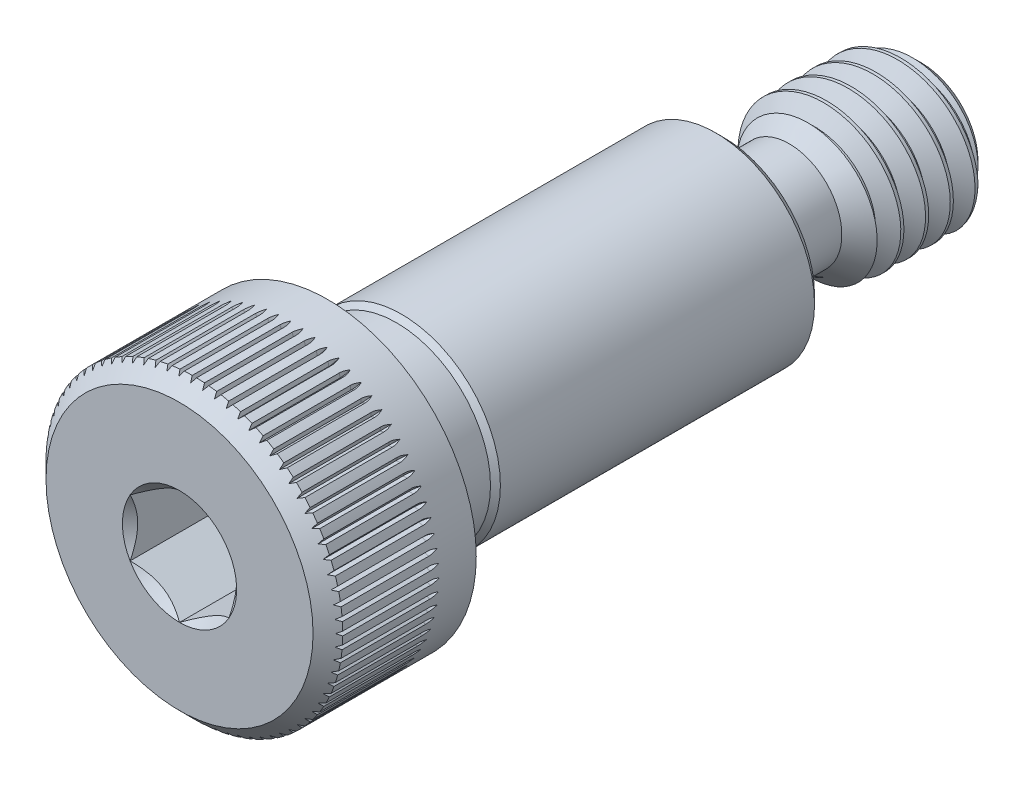
SolidWorks part; units mm, degrees
ref_plane "Front Plane" through (0, 0, 0) normal (0, 0, 1) x (1, 0, 0)
ref_plane "Top Plane" through (0, 0, 0) normal (0, 1, 0) x (1, 0, 0)
ref_plane "Right Plane" through (0, 0, 0) normal (1, 0, 0) x (0, 0, -1)
sketch "Sketch2" plane through (0, 0, 0) normal (1, 0, 0) x (0, 0, -1)
  line L0 (-11.9062, 0) -> (11.9062, 0) construction
  line L1 (-11.9062, 0) -> (-11.9062, 4.7625)
  line L2 (-11.9062, 4.7625) -> (-7.1437, 4.7625)
  line L3 (-7.1437, 4.7625) -> (-7.1437, 3.175)
  line L4 (-7.1437, 3.175) -> (5.5562, 3.175)
  line L5 (5.5562, 2.413) -> (11.9062, 2.413)
  line L6 (11.9062, 2.413) -> (11.9062, 0)
  line L7 (11.8566, 2.4989) -> (12.2535, 1.8115) construction
  line L8 (12.2535, 1.8115) -> (12.6504, 2.4989) construction
  line L9 (12.6504, 2.4989) -> (11.8566, 2.4989) construction
  line L10 (11.9062, 2.413) -> (12.6008, 2.413) construction
  line L11 (12.2535, 2.4989) -> (12.2535, 2.413) construction
  line L12 (12.2535, 2.413) -> (12.2535, 1.8974) construction
  line L13 (12.2535, 1.8974) -> (12.2535, 1.8115) construction
  line L14 (12.2039, 1.8974) -> (12.3031, 1.8974)
  line L15 (11.8814, 2.456) -> (12.6256, 2.456)
  line L16 (12.3031, 1.8974) -> (12.6256, 2.456)
  line L17 (12.2039, 1.8974) -> (11.8814, 2.456)
  line L18 (11.9062, 0) -> (11.9062, -2.413) construction
  line L19 (5.5562, -3.175) -> (5.5562, 0) construction
  line L20 (5.5562, 0) -> (5.5562, 3.175) construction
  line L21 (-11.9062, 0) -> (-11.9062, -4.7625) construction
  point P11 (-4.7815, 3.175)
  point P12 (9.9219, -2.413)
  point P22 (12.2535, 2.456)
  point P23 (4.2862, 0)
  point P25 (-4.2862, 0)
  point P26 (-7.1437, -4.7625)
  point P29 (5.5562, -3.175)
  dimension "Head Height" = 4.7625
  dimension "Shoulder Diameter" = 6.35
  dimension "Screw Size Decimal Equivalent" = 4.826
  dimension "Thread Length" = 6.35
  dimension "Head Diameter" = 9.525
  dimension "Undercut Length" = 2.3622
  dimension "Pitch" = 0.7937
  dimension "D2" = 0.0992
  dimension "D1" = 1.9844
  dimension "D3" = 7.62
  dimension "D4" = 7.62
  dimension "Shoulder Length" = 12.7
sketch "Sketch3" plane through (0, 0, 0) normal (0, 0, 1) x (1, 0, 0)
  line L1 (0, 1.8331) -> (-1.5875, 0.9165)
  line L2 (-1.5875, 0.9165) -> (-1.5875, -0.9165)
  line L3 (-1.5875, -0.9165) -> (0, -1.8331)
  line L4 (0, -1.8331) -> (1.5875, -0.9165)
  line L5 (1.5875, -0.9165) -> (1.5875, 0.9165)
  line L6 (1.5875, 0.9165) -> (0, 1.8331)
  circle A0 centre (0, 0) radius 1.5875 construction
  dimension "Drive Size" = 3.175
sketch "Sketch4" plane through (0, 0, 0) normal (1, 0, 0) x (0, 0, -1)
  line L0 (-7.1437, 4.7625) -> (-11.43, 4.7625)
  line L1 (-11.43, 4.7625) -> (-11.9062, 4.2862)
  line L2 (-7.1437, 4.7625) -> (-7.1437, 3.175)
  line L3 (-7.1437, 3.175) -> (-6.985, 3.0162)
  line L4 (-6.985, 3.0162) -> (-4.9403, 3.0162)
  line L5 (-4.9403, 3.0162) -> (-4.7815, 3.175)
  line L6 (-7.1437, 3.175) -> (5.5562, 3.175) construction
  line L7 (-11.9062, 0) -> (11.9062, 0) construction
  line L8 (-4.7815, 3.175) -> (5.3022, 3.175)
  line L9 (5.3022, 3.175) -> (5.5562, 2.921)
  line L10 (5.5562, 2.921) -> (5.5562, 0)
  line L11 (5.5562, 3.175) -> (5.5562, 2.921) construction
  line L12 (5.5562, 2.921) -> (5.5562, 2.667) construction
  line L13 (5.5562, 2.667) -> (5.5562, 2.413) construction
  line L14 (-11.9062, 4.2862) -> (-11.9062, 0)
  line L15 (-11.9062, 4.7625) -> (-7.1437, 4.7625) construction
  line L16 (-11.9062, 0) -> (5.5562, 0)
  dimension "D1" = 45
  dimension "D2" = 6.0325
  dimension "D3" = 45
  dimension "D4" = 45
  dimension "D5" = 8.5725
revolve "Revolve1" add sketch "Sketch4" angle 360 about L16
sketch "Sketch5" plane through (0, 0, 11.9062) normal (0, 0, 1) x (1, 0, 0)
  line L0 (1.5875, 0.9165) -> (0, 1.8331) construction
  line L1 (1.5875, -0.9165) -> (1.5875, 0.9165) construction
  line L2 (0, -1.8331) -> (1.5875, -0.9165) construction
  line L3 (-1.5875, -0.9165) -> (0, -1.8331) construction
  line L4 (-1.5875, 0.9165) -> (-1.5875, -0.9165) construction
  line L5 (0, 1.8331) -> (-1.5875, 0.9165) construction
  line L6 (1.5875, 0.9165) -> (0, 1.8331)
  line L7 (1.5875, -0.9165) -> (1.5875, 0.9165)
  line L8 (0, -1.8331) -> (1.5875, -0.9165)
  line L9 (-1.5875, -0.9165) -> (0, -1.8331)
  line L10 (-1.5875, 0.9165) -> (-1.5875, -0.9165)
  line L11 (0, 1.8331) -> (-1.5875, 0.9165)
extrude "Cut-Extrude1" cut sketch "Sketch5" against normal blind 3.5719
sketch "Sketch6" plane through (0, 0, 11.9062) normal (0, 0, 1) x (1, 0, 0)
  circle A0 centre (0, 0) radius 1.8331
extrude "Cut-Extrude4" cut sketch "Sketch6" against normal blind 3.5719 draft 45
sketch "Sketch7" plane through (0, 0, 0) normal (1, 0, 0) x (0, 0, -1)
  line L0 (5.5562, 2.413) -> (11.3109, 2.413)
  line L1 (5.5562, 2.413) -> (11.9062, 2.413) construction
  line L2 (11.3109, 2.413) -> (11.9062, 1.8177)
  line L3 (11.9062, 2.413) -> (11.9062, 0) construction
  line L4 (11.9062, 1.8177) -> (11.9062, 0)
  line L5 (11.9062, 0) -> (5.5562, 0)
  line L6 (5.5562, -2.921) -> (5.5562, 2.921) construction
  line L7 (5.5562, 0) -> (5.5562, 2.413)
  dimension "D1" = 45
  dimension "D2" = 0.5953
revolve "Revolve2" add sketch "Sketch7" angle 360 about L5
sketch "Sketch10" plane through (0, 0, 0) normal (1, 0, 0) x (0, 0, -1)
  line L0 (6.2801, 1.6891) -> (7.6644, 1.6891)
  line L1 (7.6644, 1.6891) -> (9.1504, 3.175)
  line L2 (9.1504, 3.175) -> (5.5562, 3.175)
  line L3 (5.5562, 3.175) -> (5.5562, 2.413)
  line L4 (5.5562, -2.921) -> (5.5562, 2.921) construction
  line L5 (11.9062, 0) -> (5.5562, 0) construction
  line L6 (-11.9062, 0) -> (11.9062, 0) construction
  arc A0 (5.5562, 2.413) -> (6.2801, 1.6891) centre (6.2801, 2.413) ccw
  dimension "Flat OD" = 3.3782
  dimension "Flat" = 2.1082
  dimension "D3" = 45
revolve "Cut-Revolve1" cut sketch "Sketch10" angle 360 about L5
sketch "Sketch8" plane through (0, 0, -11.9062) normal (0, 0, -1) x (-1, 0, 0)
  circle A0 centre (0, 0) radius 2.413 construction
  circle A1 centre (0, 0) radius 2.413
curve "Helix/Spiral1" pitch 0.7937 height 7.1437 radius 2.413 centre (0, 0, -11.9062) axis (0, 0, 1) start towards (0, 1, 0)
sketch "Sketch9" plane through (0, 0, 0) normal (1, 0, 0) x (0, 0, -1)
  line L0 (12.2039, 1.8974) -> (12.3031, 1.8974) construction
  line L1 (12.3031, 1.8974) -> (12.6256, 2.456) construction
  line L2 (11.8814, 2.456) -> (12.6256, 2.456) construction
  line L3 (12.2039, 1.8974) -> (11.8814, 2.456) construction
  line L4 (12.2039, 1.8974) -> (12.3031, 1.8974)
  line L5 (12.3031, 1.8974) -> (12.6256, 2.456)
  line L6 (11.8814, 2.456) -> (12.6256, 2.456)
  line L7 (12.2039, 1.8974) -> (11.8814, 2.456)
ref_plane "Plane1" through (0, 0, -7.6644) normal (0, 0, 1) x (1, 0, 0)
split "Split1" trim tools "Plane1" bodies to split 138 resulting bodies 139 140
sweep "Cut-Sweep1" cut profiles "Sketch9" path "Helix/Spiral1" align with end faces yes
combine bodies "Combine1" operation type add bodies to combine 141 139
sketch "Sketch11" plane through (0, 0, 11.9062) normal (0, 0, 1) x (1, 0, 0)
  line L0 (-0.0687, 4.7625) -> (0.0687, 4.7625)
  line L1 (0.0687, 4.7625) -> (0, 4.6434)
  line L2 (0, 0) -> (0, 4.7625) construction
  line L3 (0, 4.6434) -> (-0.0687, 4.7625)
  line L4 (0, 0) -> (4.7625, 0) construction
  circle A0 centre (0, 0) radius 4.7625 construction
  point P6 (0, 4.7625)
  dimension "D1" = 9.2869
  dimension "D2" = 60
  dimension "D3" = 0.1375
sketch "Sketch12" plane through (0, 0, 0) normal (1, 0, 0) x (0, 0, -1)
  line L0 (-11.9062, 4.6434) -> (-8.6218, 4.6434)
  line L1 (-8.2153, 5.0499) -> (-8.2153, 4.7625) construction
  line L2 (-11.9062, 4.7625) -> (-7.1437, 4.7625) construction
  arc A0 (-8.6218, 4.6434) -> (-8.2153, 5.0499) centre (-8.6218, 5.0499) ccw
  point P11 (-8.3344, 4.7625)
  dimension "D1" = 1.1906
sweep "Cut-Sweep2" cut profiles "Sketch11" path "Sketch12"
pattern_circular "CirPattern1" count 76 over 360 about axis through (0, 0, 11.9062) along (0, 0, -1) of "Cut-Sweep2"
equation "\"D2@Sketch2\" = \"Pitch@Sketch2\" / 8"
equation "\"D1@Sketch2\"=\"Pitch@Sketch2\"*2.5"
equation "\"D2@Sketch4\"=\"Shoulder Diameter@Sketch2\"*0.95"
equation "\"D5@Sketch4\"=\"Head Diameter@Sketch2\"*0.9"
equation "\"D1@Cut-Extrude1\"=\"Head Height@Sketch2\"*0.75"
equation "\"D1@Cut-Extrude4\"=\"D1@Cut-Extrude1\""
equation "\"D2@Sketch7\"=\"pitch@sketch2\"*0.75"
equation "\"D3@Helix/Spiral1\"=\"Thread Length@Sketch2\"+\"Pitch@Sketch2\""
equation "\"D4@Helix/Spiral1\"=\"Pitch@Sketch2\""
equation "\"D1@Sketch11\"=\"Head Diameter@Sketch2\"*0.975"
equation "\"D1@Sketch12\"=\"Head Height@Sketch2\"*0.25"
equation "\"D1@CirPattern1\"=\"Head Diameter@Sketch2\" * 3.14 / \"D3@Sketch11\" * 0.35"
equation "\"D3@Sketch2\"=\"Thread Length@Sketch2\"*1.2"
equation "\"D4@Sketch2\"=\"D3@Sketch2\""
